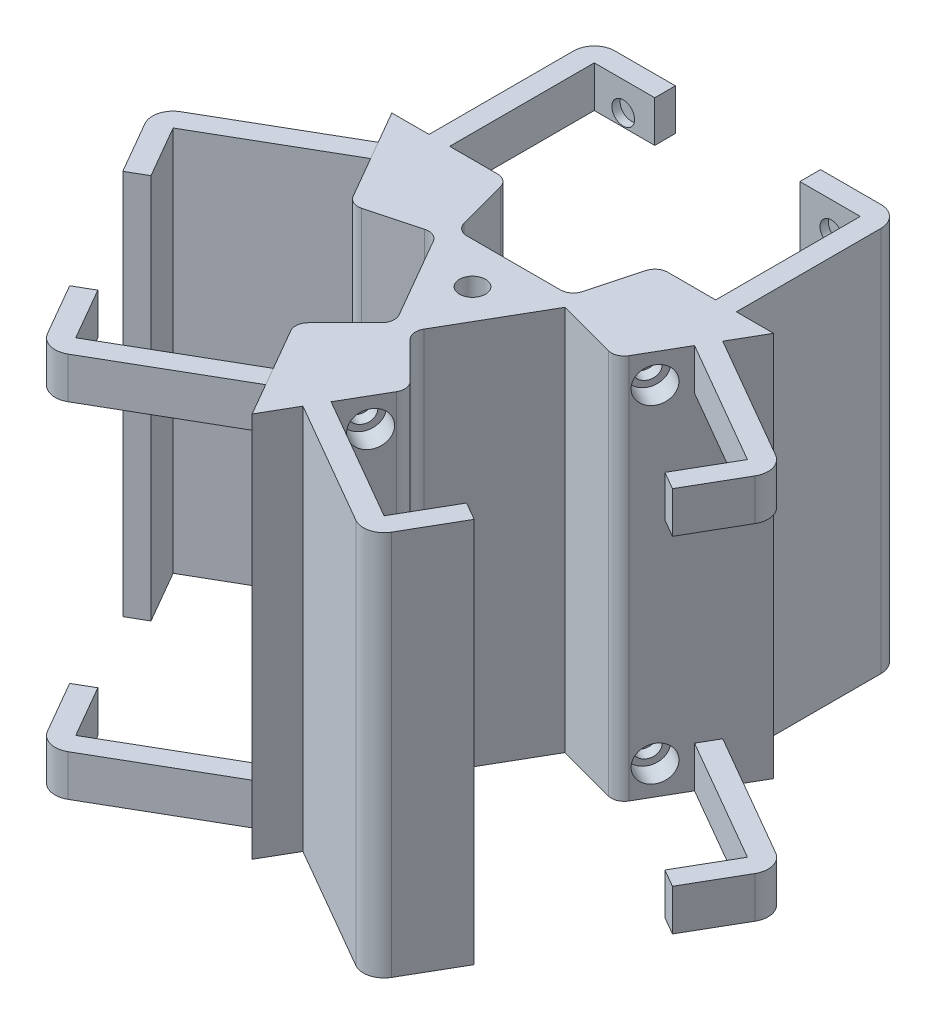
SolidWorks part; units mm, degrees
ref_plane "Alzado" through (0, 0, 0) normal (0, 0, 1) x (1, 0, 0)
ref_plane "Planta" through (0, 0, 0) normal (0, 1, 0) x (1, 0, 0)
ref_plane "Vista lateral" through (0, 0, 0) normal (1, 0, 0) x (0, 0, -1)
sketch "Croquis1" plane through (0, 0, 0) normal (0, 1, 0) x (1, 0, 0)
  line L0 (0, 50.8) -> (0, -50.8) construction
  line L1 (-50.8, 0) -> (50.8, 0) construction
  line L2 (0, 0) -> (-35.921, -35.921) construction
  line L3 (0, 0) -> (35.921, -35.921) construction
  line L10 (0, -17.5) -> (-15.1554, 8.75) construction
  line L11 (-15.1554, 8.75) -> (15.1554, 8.75) construction
  line L12 (15.1554, 8.75) -> (0, -17.5) construction
  line L13 (-1.2978, -16.7522) -> (-15.1813, 7.2027) construction
  line L14 (1.2978, -16.7522) -> (15.1813, 7.2027) construction
  line L15 (-13.8835, 9.4549) -> (13.8835, 9.4549) construction
  line L16 (1.6964, -16.0645) -> (13.335, -27.7031)
  line L17 (13.335, -27.7031) -> (0, -50.8)
  line L18 (0, -50.8) -> (-13.335, -27.7031)
  line L19 (-13.335, -27.7031) -> (-1.6964, -16.0645)
  line L20 (-17.3241, 25.4) -> (-13.0641, 9.5013)
  line L21 (-43.9941, 25.4) -> (-17.3241, 25.4)
  line L22 (-30.6591, 2.3031) -> (-43.9941, 25.4)
  line L23 (-14.7604, 6.5631) -> (-30.6591, 2.3031)
  line L24 (30.6591, 2.3031) -> (14.7604, 6.5631)
  line L25 (43.9941, 25.4) -> (30.6591, 2.3031)
  line L26 (17.3241, 25.4) -> (43.9941, 25.4)
  line L27 (13.0641, 9.5013) -> (17.3241, 25.4)
  line L28 (-14.7604, 6.5631) -> (-1.6964, -16.0645)
  line L29 (1.6964, -16.0645) -> (14.7604, 6.5631)
  line L30 (-13.0641, 9.5013) -> (13.0641, 9.5013)
  line L31 (-43.9941, 25.4) -> (0, -50.8) construction
  line L32 (43.9941, 25.4) -> (0, -50.8) construction
  line L33 (-43.9941, 25.4) -> (43.9941, 25.4) construction
  circle A0 centre (0, 0) radius 50.8 construction
  circle A7 centre (0, 0) radius 17.5 construction
  circle A8 centre (-13.8835, 7.9549) radius 1.5 construction
  circle A9 centre (13.8835, 7.9549) radius 1.5 construction
  circle A10 centre (0, -16) radius 1.5 construction
  arc A11 (-15.1813, 7.2027) -> (-13.8835, 9.4549) centre (-13.8835, 7.9549) cw construction
  arc A12 (15.1813, 7.2027) -> (13.8835, 9.4549) centre (13.8835, 7.9549) ccw construction
  arc A13 (1.2978, -16.7522) -> (-1.2978, -16.7522) centre (0, -16) cw construction
  arc A14 (-15.1813, 7.2027) -> (-13.8835, 9.4549) centre (-13.8835, 7.9549) cw construction
  arc A15 (13.8835, 9.4549) -> (15.1813, 7.2027) centre (13.8835, 7.9549) cw construction
  arc A16 (-1.2978, -16.7522) -> (1.2978, -16.7522) centre (0, -16) ccw construction
  circle A17 centre (0, 0) radius 76.2 construction
  point P45 (0, 0)
  dimension "D1" = 101.6
  dimension "D6" = 13.8835
  dimension "D9" = 3
  dimension "D5" = 3
  dimension "D4" = 35
  dimension "D10" = 152.4
  dimension "D2" = 45
  dimension "D3" = 45
  dimension "D7" = 26.67
extrude "Saliente-Extruir1" add sketch "Croquis1" along normal blind 88.9
sketch "Croquis4" plane through (0, 88.9, 0) normal (0, 1, 0) x (1, 0, 0)
  circle A0 centre (0, 0) radius 3
  dimension "D1" = 6
extrude "Cortar-Extruir1" cut sketch "Croquis4" against normal through all
fillet "Redondeo6" radius 3 5 edges at (-14.7604, 44.45, -6.5631) (1.6964, 44.45, 16.0645) (-1.6964, 44.45, 16.0645) (-13.0641, 44.45, -9.5013) (13.0641, 44.45, -9.5013)
fillet "Redondeo7" radius 3 6 edges at (-17.3241, 44.45, -25.4) (-30.6591, 44.45, -2.3031) (17.3241, 44.45, -25.4) (-13.335, 44.45, 27.7031) (30.6591, 44.45, -2.3031) (13.335, 44.45, 27.7031)
scale "Escala2" scale about centroid uniform scaling yes scale factor 1.05
sketch "Croquis9" plane through (0, 91.1225, 0) normal (0, 1, 0) x (1, 0, 0)
  line L9 (0, 76.2) -> (0, -76.2) construction
  line L10 (76.2, 0) -> (-76.2, 0) construction
  line L41 (-37.1934, 26.6702) -> (-37.1934, 61.6702)
  line L43 (-20.607, 26.6702) -> (-46.1934, 26.6702) construction
  line L44 (-32.1934, 66.6702) -> (-17.5643, 66.6702)
  line L45 (-17.5643, 66.6702) -> (-17.5643, 61.6702)
  line L46 (-17.5643, 61.6702) -> (-32.1934, 61.6702)
  line L47 (-32.1934, 61.6702) -> (-32.1934, 26.6702)
  line L48 (-32.1934, 26.6702) -> (-37.1934, 26.6702)
  line L49 (32.1934, 61.6702) -> (32.1934, 26.6702)
  line L50 (17.5643, 61.6702) -> (32.1934, 61.6702)
  line L51 (17.5643, 66.6702) -> (17.5643, 61.6702)
  line L52 (32.1934, 66.6702) -> (17.5643, 66.6702)
  line L53 (37.1934, 26.6702) -> (37.1934, 61.6702)
  line L54 (32.1934, 26.6702) -> (37.1934, 26.6702)
  line L55 (39.1937, 14.5452) -> (41.6937, 18.8753)
  line L56 (41.6937, 18.8753) -> (72.0046, 1.3753)
  line L57 (73.8347, -5.4548) -> (66.5202, -18.1239)
  line L58 (66.5202, -18.1239) -> (62.1901, -15.6239)
  line L59 (62.1901, -15.6239) -> (69.5046, -2.9548)
  line L60 (69.5046, -2.9548) -> (39.1937, 14.5452)
  line L61 (37.3112, -58.7154) -> (7.0003, -41.2154)
  line L62 (7.0003, -41.2154) -> (4.5003, -45.5455)
  line L63 (4.5003, -45.5455) -> (34.8112, -63.0455)
  line L64 (41.6414, -61.2154) -> (48.9559, -48.5462)
  line L65 (48.9559, -48.5462) -> (44.6258, -46.0462)
  line L66 (44.6258, -46.0462) -> (37.3112, -58.7154)
  line L67 (-7.0003, -41.2154) -> (-4.5003, -45.5455)
  line L68 (-4.5003, -45.5455) -> (-34.8112, -63.0455)
  line L69 (-41.6414, -61.2154) -> (-48.9559, -48.5462)
  line L70 (-48.9559, -48.5462) -> (-44.6258, -46.0462)
  line L71 (-44.6258, -46.0462) -> (-37.3112, -58.7154)
  line L72 (-37.3112, -58.7154) -> (-7.0003, -41.2154)
  line L73 (-69.5046, -2.9548) -> (-39.1937, 14.5452)
  line L74 (-39.1937, 14.5452) -> (-41.6937, 18.8753)
  line L75 (-41.6937, 18.8753) -> (-72.0046, 1.3753)
  line L76 (-73.8347, -5.4548) -> (-66.5202, -18.1239)
  line L77 (-66.5202, -18.1239) -> (-62.1901, -15.6239)
  line L78 (-62.1901, -15.6239) -> (-69.5046, -2.9548)
  circle A0 centre (0, 0) radius 101.6 construction
  circle A1 centre (0, 0) radius 76.2 construction
  arc A8 (-37.1934, 61.6702) -> (-32.1934, 66.6702) centre (-32.1934, 61.6702) cw
  arc A9 (37.1934, 61.6702) -> (32.1934, 66.6702) centre (32.1934, 61.6702) ccw
  arc A10 (72.0046, 1.3753) -> (73.8347, -5.4548) centre (69.5046, -2.9548) cw
  arc A11 (34.8112, -63.0455) -> (41.6414, -61.2154) centre (37.3112, -58.7154) ccw
  arc A12 (-34.8112, -63.0455) -> (-41.6414, -61.2154) centre (-37.3112, -58.7154) cw
  arc A13 (-72.0046, 1.3753) -> (-73.8347, -5.4548) centre (-69.5046, -2.9548) ccw
  point P13 (0, 0)
  point P26 (0, 0)
  point P56 (-1.3626, -0.7865)
  point P58 (0, 0)
  dimension "D1" = 152.4
  dimension "D2" = 203.2
  dimension "D3" = 5
  dimension "D4" = 9
  dimension "D5" = 35
  dimension "D6" = 3
sketch "Croquis12" plane through (0, 91.1225, 0) normal (0, 1, 0) x (1, 0, 0)
  line L0 (0, 101.6) -> (0, -101.6) construction
  circle A0 centre (0, 0) radius 76.2 construction
  circle A1 centre (0, 0) radius 101.6 construction
  dimension "D1" = 152.4
  dimension "D2" = 203.2
extrude "Saliente-Extruir2" add sketch "Croquis9" against normal through all
sketch "Croquis14" plane through (0, 0, -66.6702) normal (0, 0, -1) x (-1, 0, 0)
  line L0 (-32.1934, -2.2225) -> (-32.1934, 91.1225) construction
  line L1 (17.5643, 91.1225) -> (32.1934, 91.1225) construction
  circle A0 centre (25.1934, 84.1225) radius 2.75
  circle A1 centre (25.1934, 4.7775) radius 2.75
  circle A2 centre (-25.1934, 4.7775) radius 2.75
  circle A3 centre (-25.1934, 84.1225) radius 2.75
  point P15 (0, 0)
  point P16 (0, 0)
  dimension "D1" = 5.5
  dimension "D2" = 7
  dimension "D3" = 7
  dimension "D4" = 7
  dimension "D5" = 7
  dimension "D6" = 7
  dimension "D7" = 7
extrude "Cortar-Extruir2" cut sketch "Croquis14" along normal blind 2 from surface starting at face at (24.8788, 44.45, -61.6702)
sketch "Croquis15" plane through (0, 0, -26.6702) normal (0, 0, -1) x (-1, 0, 0)
  line L0 (32.1934, -2.2225) -> (32.1934, 91.1225) construction
  line L1 (-32.1934, -2.2225) -> (-20.6078, -2.2225) construction
  line L2 (-32.1934, 91.1225) -> (-20.6078, 91.1225) construction
  circle A0 centre (-25.1934, 4.7775) radius 4.25
  circle A1 centre (25.1934, 4.7775) radius 4.25
  circle A2 centre (-25.1934, 84.1225) radius 4.25
  circle A3 centre (25.1934, 84.1225) radius 4.25
  point P15 (0, 0)
  point P16 (0, 0)
  point P17 (0, 0)
  dimension "D1" = 8.5
  dimension "D2" = 7
  dimension "D3" = 7
  dimension "D4" = 7
  dimension "D5" = 7
  dimension "D6" = 7
  dimension "D7" = 7
extrude "Cortar-Extruir3" cut sketch "Croquis15" against normal blind 5.5
sketch "Croquis16" plane through (0, 0, -21.1702) normal (0, 0, -1) x (-1, 0, 0)
  circle A0 centre (-25.1934, 4.7775) radius 2.75
  circle A1 centre (25.1934, 4.7775) radius 2.75
  circle A2 centre (25.1934, 84.1225) radius 2.75
  circle A3 centre (-25.1934, 84.1225) radius 2.75
  dimension "D1" = 5.5
extrude "Cortar-Extruir4" cut sketch "Croquis16" against normal blind 3
pattern_circular "MatrizC7" count 3 over 360 about axis through (0.0004, -2.2225, -0.0002) along (0, 1, 0) of "Cortar-Extruir4", "Cortar-Extruir3"
sketch "Croquis17" plane through (18.5967, 0, -32.2104) normal (0.5, 0, -0.866) x (-0.866, 0, -0.5)
  line L0 (-26.6703, 91.1225) -> (-26.6703, -2.2225) construction
  line L1 (-26.6703, 81.1225) -> (-68.6703, 81.1225)
  line L2 (-26.6703, 81.1225) -> (-26.6703, 7.7775)
  line L3 (-26.6703, 7.7775) -> (-68.6703, 7.7775)
  line L4 (-68.6703, 81.1225) -> (-68.6703, 7.7775)
  line L5 (76.2, 91.1225) -> (-76.2, 91.1225) construction
  line L6 (-61.6702, -2.2225) -> (-26.6703, -2.2225) construction
  dimension "D1" = 42
  dimension "D2" = 10
  dimension "D3" = 10
extrude "Cortar-Extruir5" cut sketch "Croquis17" against normal blind 31
sketch "Croquis18" plane through (-37.1934, 0, 0) normal (-1, 0, 0) x (0, 0, 1)
  line L0 (-26.6702, 91.1225) -> (-26.6702, -2.2225) construction
  line L1 (-26.6702, 81.1225) -> (-71.6702, 81.1225)
  line L2 (-26.6702, 81.1225) -> (-26.6702, 7.7775)
  line L3 (-26.6702, 7.7775) -> (-71.6702, 7.7775)
  line L4 (-71.6702, 81.1225) -> (-71.6702, 7.7775)
  line L5 (101.6, 91.1225) -> (-101.6, 91.1225) construction
  line L6 (-61.6702, -2.2225) -> (-26.6702, -2.2225) construction
  dimension "D1" = 10
  dimension "D2" = 10
  dimension "D3" = 45
extrude "Cortar-Extruir6" cut sketch "Croquis18" against normal blind 31
sketch "Croquis20" plane through (18.5967, 0, 32.2104) normal (0.5, 0, 0.866) x (0.866, 0, -0.5)
  line L8 (-26.6696, 91.1225) -> (-26.6696, -2.2225) construction
  line L9 (-87.2978, 81.1225) -> (-26.6696, 81.1225)
  line L10 (-87.2978, 81.1225) -> (-87.2978, 7.7775)
  line L11 (-87.2978, 7.7775) -> (-26.6696, 7.7775)
  line L12 (-26.6696, 81.1225) -> (-26.6696, 7.7775)
  line L13 (-61.6702, -2.2225) -> (-26.6702, -2.2225) construction
  line L14 (101.6, 91.1225) -> (-101.6, 91.1225) construction
  dimension "D1" = 60.6282
  dimension "D2" = 10
  dimension "D3" = 10
extrude "Cortar-Extruir7" cut sketch "Croquis20" against normal blind 36
